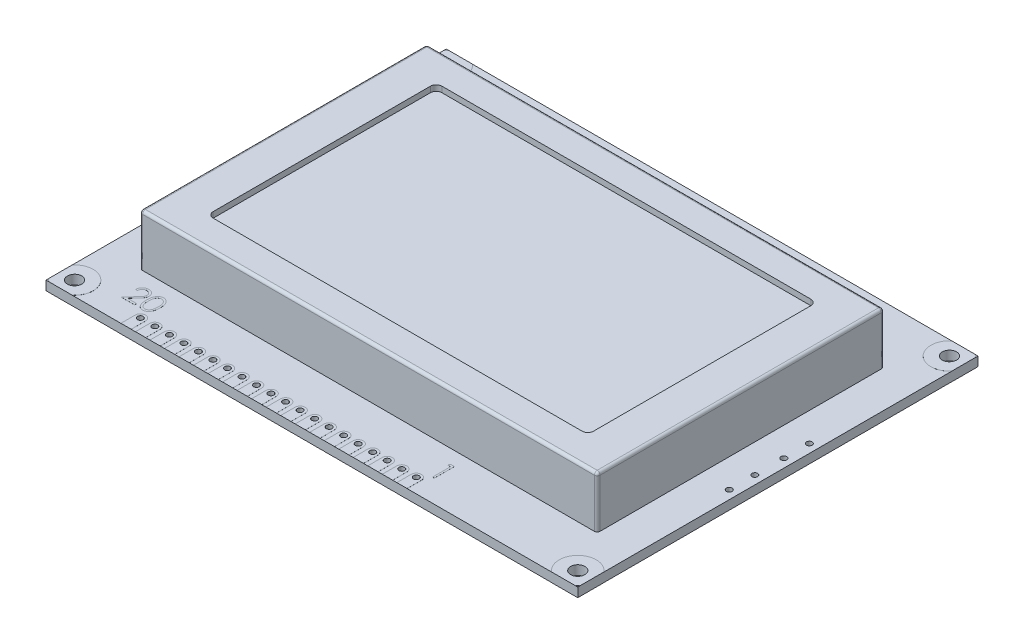
SolidWorks part; units mm, degrees
material "A-Glass Fiber"
ref_plane "Front Plane" through (0, 0, 0) normal (0, 0, 1) x (1, 0, 0)
ref_plane "Top Plane" through (0, 0, 0) normal (0, 1, 0) x (1, 0, 0)
ref_plane "Right Plane" through (0, 0, 0) normal (1, 0, 0) x (0, 0, -1)
sketch "Sketch1" plane through (0, 0, 0) normal (0, 1, 0) x (1, 0, 0)
  line L0 (2.5, 67.5) -> (90.5, 67.5) construction
  line L1 (0, 0) -> (93, 0)
  line L2 (0, 0) -> (0, 70)
  line L3 (0, 70) -> (93, 70)
  line L4 (93, 0) -> (93, 70)
  line L5 (2.5, 2.5) -> (90.5, 2.5) construction
  line L6 (90.5, 2.5) -> (90.5, 67.5) construction
  line L7 (2.5, 67.5) -> (2.5, 2.5) construction
  line L8 (90.5, 35) -> (91.5, 35) construction
  line L9 (91.5, 37.54) -> (91.5, 32.46) construction
  line L10 (91.5, 37.54) -> (91.5, 42) construction
  line L11 (91.5, 32.46) -> (91.5, 28) construction
  circle A0 centre (2.5, 67.5) radius 1.25
  circle A1 centre (90.5, 67.5) radius 1.25
  circle A2 centre (90.5, 2.5) radius 1.25
  circle A3 centre (2.5, 2.5) radius 1.25
  circle A4 centre (14, 2.5) radius 0.5
  circle A5 centre (16.54, 2.5) radius 0.5
  circle A6 centre (19.08, 2.5) radius 0.5
  circle A7 centre (21.62, 2.5) radius 0.5
  circle A8 centre (24.16, 2.5) radius 0.5
  circle A9 centre (26.7, 2.5) radius 0.5
  circle A10 centre (29.24, 2.5) radius 0.5
  circle A11 centre (31.78, 2.5) radius 0.5
  circle A12 centre (34.32, 2.5) radius 0.5
  circle A13 centre (36.86, 2.5) radius 0.5
  circle A14 centre (39.4, 2.5) radius 0.5
  circle A15 centre (41.94, 2.5) radius 0.5
  circle A16 centre (44.48, 2.5) radius 0.5
  circle A17 centre (47.02, 2.5) radius 0.5
  circle A18 centre (49.56, 2.5) radius 0.5
  circle A19 centre (52.1, 2.5) radius 0.5
  circle A20 centre (54.64, 2.5) radius 0.5
  circle A21 centre (57.18, 2.5) radius 0.5
  circle A22 centre (59.72, 2.5) radius 0.5
  circle A23 centre (62.26, 2.5) radius 0.5
  circle A24 centre (91.5, 42) radius 0.5
  circle A25 centre (91.5, 37.54) radius 0.5
  circle A26 centre (91.5, 32.46) radius 0.5
  circle A27 centre (91.5, 28) radius 0.5
  point P57 (91.5, 35)
  dimension "D3" = 2.5
  dimension "D9" = 1
  dimension "D13" = 1
  dimension "D1" = 93
  dimension "D2" = 70
  dimension "D4" = 2.5
  dimension "D5" = 2.5
  dimension "D6" = 2.5
  dimension "D7" = 2.5
  dimension "D8" = 14
  dimension "D11" = 5.08
  dimension "D12" = 14
  dimension "D14" = 1.5
  dimension "D10" = 20
extrude "Boss-Extrude1" add sketch "Sketch1" along normal blind 1.6
sketch "Sketch4" plane through (0, 0, 0) normal (0, 1, 0) x (1, 0, 0)
  line L0 (13.1, 2.5) -> (13.1, 0)
  line L1 (0, 0) -> (93, 0) construction
  line L2 (13.1, 0) -> (14.9, 0)
  line L3 (14.9, 0) -> (14.9, 2.5)
  line L4 (15.64, 2.5) -> (15.64, 0)
  line L5 (15.64, 0) -> (17.44, 0)
  line L6 (17.44, 0) -> (17.44, 2.5)
  line L7 (18.18, 2.5) -> (18.18, 0)
  line L8 (18.18, 0) -> (19.98, 0)
  line L9 (19.98, 0) -> (19.98, 2.5)
  line L10 (20.72, 2.5) -> (20.72, 0)
  line L11 (20.72, 0) -> (22.52, 0)
  line L12 (22.52, 0) -> (22.52, 2.5)
  line L13 (23.26, 2.5) -> (23.26, 0)
  line L14 (23.26, 0) -> (25.06, 0)
  line L15 (25.06, 0) -> (25.06, 2.5)
  line L16 (25.8, 2.5) -> (25.8, 0)
  line L17 (25.8, 0) -> (27.6, 0)
  line L18 (27.6, 0) -> (27.6, 2.5)
  line L19 (28.34, 2.5) -> (28.34, 0)
  line L20 (28.34, 0) -> (30.14, 0)
  line L21 (30.14, 0) -> (30.14, 2.5)
  line L22 (30.88, 2.5) -> (30.88, 0)
  line L23 (30.88, 0) -> (32.68, 0)
  line L24 (32.68, 0) -> (32.68, 2.5)
  line L25 (33.42, 2.5) -> (33.42, 0)
  line L26 (33.42, 0) -> (35.22, 0)
  line L27 (35.22, 0) -> (35.22, 2.5)
  line L28 (35.96, 2.5) -> (35.96, 0)
  line L29 (35.96, 0) -> (37.76, 0)
  line L30 (37.76, 0) -> (37.76, 2.5)
  line L31 (38.5, 2.5) -> (38.5, 0)
  line L32 (38.5, 0) -> (40.3, 0)
  line L33 (40.3, 0) -> (40.3, 2.5)
  line L34 (41.04, 2.5) -> (41.04, 0)
  line L35 (41.04, 0) -> (42.84, 0)
  line L36 (42.84, 0) -> (42.84, 2.5)
  line L37 (43.58, 2.5) -> (43.58, 0)
  line L38 (43.58, 0) -> (45.38, 0)
  line L39 (45.38, 0) -> (45.38, 2.5)
  line L40 (46.12, 2.5) -> (46.12, 0)
  line L41 (46.12, 0) -> (47.92, 0)
  line L42 (47.92, 0) -> (47.92, 2.5)
  line L43 (48.66, 2.5) -> (48.66, 0)
  line L44 (48.66, 0) -> (50.46, 0)
  line L45 (50.46, 0) -> (50.46, 2.5)
  line L46 (51.2, 2.5) -> (51.2, 0)
  line L47 (51.2, 0) -> (53, 0)
  line L48 (53, 0) -> (53, 2.5)
  line L49 (53.74, 2.5) -> (53.74, 0)
  line L50 (53.74, 0) -> (55.54, 0)
  line L51 (55.54, 0) -> (55.54, 2.5)
  line L52 (56.28, 2.5) -> (56.28, 0)
  line L53 (56.28, 0) -> (58.08, 0)
  line L54 (58.08, 0) -> (58.08, 2.5)
  line L55 (58.82, 2.5) -> (58.82, 0)
  line L56 (58.82, 0) -> (60.62, 0)
  line L57 (60.62, 0) -> (60.62, 2.5)
  line L58 (61.36, 2.5) -> (61.36, 0)
  line L59 (61.36, 0) -> (63.16, 0)
  line L60 (63.16, 0) -> (63.16, 2.5)
  line L61 (0, 4.5767) -> (0, 0.4233)
  line L62 (0, 70) -> (0, 0) construction
  line L63 (0.4233, 0) -> (4.5767, 0)
  line L64 (4.5767, 70) -> (0.4233, 70)
  line L65 (93, 70) -> (0, 70) construction
  line L66 (0, 69.5767) -> (0, 65.4233)
  line L67 (88.4233, 70) -> (92.5767, 70)
  line L68 (93, 69.5767) -> (93, 65.4233)
  line L69 (93, 0) -> (93, 70) construction
  line L70 (88.4233, 0) -> (92.5767, 0)
  line L71 (93, 4.5767) -> (93, 0.4233)
  arc A0 (13.1, 2.5) -> (14.9, 2.5) centre (14, 2.5) cw
  circle A1 centre (14, 2.5) radius 0.5
  arc A2 (15.64, 2.5) -> (17.44, 2.5) centre (16.54, 2.5) cw
  circle A3 centre (16.54, 2.5) radius 0.5
  arc A4 (18.18, 2.5) -> (19.98, 2.5) centre (19.08, 2.5) cw
  circle A5 centre (19.08, 2.5) radius 0.5
  arc A6 (20.72, 2.5) -> (22.52, 2.5) centre (21.62, 2.5) cw
  circle A7 centre (21.62, 2.5) radius 0.5
  arc A8 (23.26, 2.5) -> (25.06, 2.5) centre (24.16, 2.5) cw
  circle A9 centre (24.16, 2.5) radius 0.5
  arc A10 (25.8, 2.5) -> (27.6, 2.5) centre (26.7, 2.5) cw
  circle A11 centre (26.7, 2.5) radius 0.5
  arc A12 (28.34, 2.5) -> (30.14, 2.5) centre (29.24, 2.5) cw
  circle A13 centre (29.24, 2.5) radius 0.5
  arc A14 (30.88, 2.5) -> (32.68, 2.5) centre (31.78, 2.5) cw
  circle A15 centre (31.78, 2.5) radius 0.5
  arc A16 (33.42, 2.5) -> (35.22, 2.5) centre (34.32, 2.5) cw
  circle A17 centre (34.32, 2.5) radius 0.5
  arc A18 (35.96, 2.5) -> (37.76, 2.5) centre (36.86, 2.5) cw
  circle A19 centre (36.86, 2.5) radius 0.5
  arc A20 (38.5, 2.5) -> (40.3, 2.5) centre (39.4, 2.5) cw
  circle A21 centre (39.4, 2.5) radius 0.5
  arc A22 (41.04, 2.5) -> (42.84, 2.5) centre (41.94, 2.5) cw
  circle A23 centre (41.94, 2.5) radius 0.5
  arc A24 (43.58, 2.5) -> (45.38, 2.5) centre (44.48, 2.5) cw
  circle A25 centre (44.48, 2.5) radius 0.5
  arc A26 (46.12, 2.5) -> (47.92, 2.5) centre (47.02, 2.5) cw
  circle A27 centre (47.02, 2.5) radius 0.5
  arc A28 (48.66, 2.5) -> (50.46, 2.5) centre (49.56, 2.5) cw
  circle A29 centre (49.56, 2.5) radius 0.5
  arc A30 (51.2, 2.5) -> (53, 2.5) centre (52.1, 2.5) cw
  circle A31 centre (52.1, 2.5) radius 0.5
  arc A32 (53.74, 2.5) -> (55.54, 2.5) centre (54.64, 2.5) cw
  circle A33 centre (54.64, 2.5) radius 0.5
  arc A34 (56.28, 2.5) -> (58.08, 2.5) centre (57.18, 2.5) cw
  circle A35 centre (57.18, 2.5) radius 0.5
  arc A36 (58.82, 2.5) -> (60.62, 2.5) centre (59.72, 2.5) cw
  circle A37 centre (59.72, 2.5) radius 0.5
  arc A38 (61.36, 2.5) -> (63.16, 2.5) centre (62.26, 2.5) cw
  circle A39 centre (62.26, 2.5) radius 0.5
  arc A40 (0, 0.4233) -> (0.4233, 0) centre (2.5, 2.5) ccw
  circle A41 centre (2.5, 2.5) radius 1.25
  circle A42 centre (90.5, 67.5) radius 1.25
  arc A43 (88.4233, 70) -> (93, 65.4233) centre (90.5, 67.5) ccw
  circle A44 centre (2.5, 67.5) radius 1.25
  arc A45 (0.4233, 70) -> (0, 69.5767) centre (2.5, 67.5) ccw
  circle A46 centre (90.5, 2.5) radius 1.25
  arc A47 (93, 4.5767) -> (88.4233, 0) centre (90.5, 2.5) ccw
  arc A48 (4.5767, 0) -> (0, 4.5767) centre (2.5, 2.5) ccw
  arc A49 (0, 65.4233) -> (4.5767, 70) centre (2.5, 67.5) ccw
  arc A50 (93, 69.5767) -> (92.5767, 70) centre (90.5, 67.5) ccw
  arc A51 (92.5767, 0) -> (93, 0.4233) centre (90.5, 2.5) ccw
  dimension "D1" = 20
  dimension "D2" = 0.9
  dimension "D3" = 6.5
extrude "Boss-Extrude2" add sketch "Sketch4" along normal blind 1.61 and the other way blind 0.01
sketch "Sketch5" plane through (0, 0, 0) normal (0, 1, 0) x (1, 0, 0)
  line L0 (0, 70) -> (93, 0) construction
  line L2 (6.5, 60.1) -> (86.5, 60.1)
  line L3 (6.5, 60.1) -> (6.5, 9.9)
  line L4 (6.5, 9.9) -> (86.5, 9.9)
  line L5 (86.5, 60.1) -> (86.5, 9.9)
  line L6 (6.5, 60.1) -> (86.5, 9.9) construction
  line L7 (6.5, 9.9) -> (86.5, 60.1) construction
  point P4 (46.5, 35)
  dimension "D1" = 50.2
  dimension "D2" = 80
extrude "Boss-Extrude3" add sketch "Sketch5" along normal blind 9 from surface starting at face at (91.5, 1.6, -27.5)
fillet "Fillet1" radius 0.5 8 edges at (86.5, 6.1, -9.9) (86.5, 6.1, -60.1) (86.5, 10.6, -35) (46.5, 10.6, -60.1) (6.5, 6.1, -60.1) (46.5, 10.6, -9.9) (6.5, 10.6, -35) (6.5, 6.1, -9.9)
sketch "Sketch6" plane through (0, 0, 0) normal (0, 1, 0) x (1, 0, 0)
  line L0 (0, 70) -> (93, 0) construction
  line L2 (14.24, 55) -> (78.76, 55)
  line L3 (13.24, 54) -> (13.24, 16)
  line L4 (14.24, 15) -> (78.76, 15)
  line L5 (79.76, 54) -> (79.76, 16)
  line L6 (13.24, 55) -> (79.76, 15) construction
  line L7 (13.24, 15) -> (79.76, 55) construction
  arc A0 (78.76, 55) -> (79.76, 54) centre (78.76, 54) cw
  arc A1 (78.76, 15) -> (79.76, 16) centre (78.76, 16) ccw
  arc A2 (13.24, 16) -> (14.24, 15) centre (14.24, 16) ccw
  arc A3 (14.24, 55) -> (13.24, 54) centre (14.24, 54) ccw
  point P4 (46.5, 35)
  dimension "D3" = 1
  dimension "D1" = 66.52
  dimension "D2" = 40
extrude "Cut-Extrude1" cut sketch "Sketch6" against normal blind 1 from surface starting at face at (46.5, 10.6, -35)
sketch "Sketch7" plane through (0, 0, 0) normal (0, 1, 0) x (1, 0, 0)
  text T0 "1"
  text T1 "20"
extrude "Boss-Extrude4" add sketch "Sketch7" along normal blind 0.01 from surface starting at face at (38.8909, 1.6, -4.5227)
sketch "Sketch8" plane through (0, 0, 0) normal (0, 1, 0) x (1, 0, 0)
  circle A0 centre (19.3751, 34.1638) radius 7.5
  circle A1 centre (38.6082, 39.2856) radius 7.5
  circle A2 centre (59.3046, 35.4181) radius 7.5
  dimension "D1" = 15
extrude "Boss-Extrude5" add sketch "Sketch8" against normal blind 3
fillet "Fillet2" radius 9 3 edges at (59.3046, -3, -27.9181) (38.6082, -3, -31.7856) (19.3751, -3, -26.6638)
sketch "Sketch9" plane through (0, 1.6, 0) normal (0, 1, 0) x (1, 0, 0)
